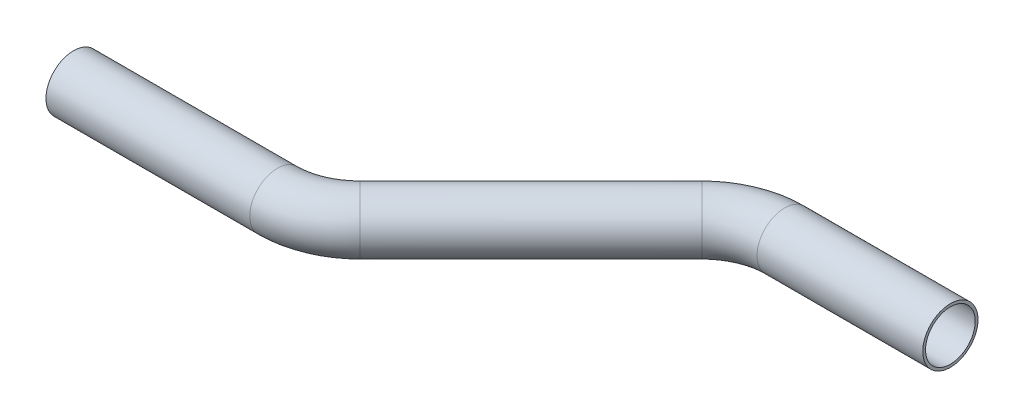
SolidWorks part; units mm, degrees
ref_plane "Front Plane" through (0, 0, 0) normal (0, 0, 1) x (1, 0, 0)
ref_plane "Top Plane" through (0, 0, 0) normal (0, 1, 0) x (1, 0, 0)
ref_plane "Right Plane" through (0, 0, 0) normal (1, 0, 0) x (0, 0, -1)
sketch "Sketch1" plane through (0, 0, 0) normal (0, 1, 0) x (1, 0, 0)
  line L0 (0, 0) -> (46.8479, 0)
  line L1 (60.3183, 5.5796) -> (99.5752, 44.8365)
  line L2 (113.0456, 50.4161) -> (151.1456, 50.4161)
  arc A1 (99.5752, 44.8365) -> (113.0456, 50.4161) centre (113.0456, 31.3661) cw
  arc A2 (46.8479, 0) -> (60.3183, 5.5796) centre (46.8479, 19.05) ccw
  point P10 (105.1548, 50.4161)
  point P14 (54.7387, 0)
  dimension "D3" = 19.05
  dimension "D1" = 54.7387
  dimension "D2" = 38.1
  dimension "D4" = 45
  dimension "D5" = 50.4161
ref_plane "Plane1" through (0, 0, 0) normal (1, 0, 0) x (0, 0, -1)
sketch "Sketch2" plane through (0, 0, 0) normal (1, 0, 0) x (0, 0, -1)
  circle A0 centre (0, 0) radius 6.35
  circle A1 centre (0, 0) radius 5.715
  dimension "D1" = 12.7
  dimension "D2" = 0.635
sweep "Sweep1" add profiles "Sketch2" path "Sketch1"
